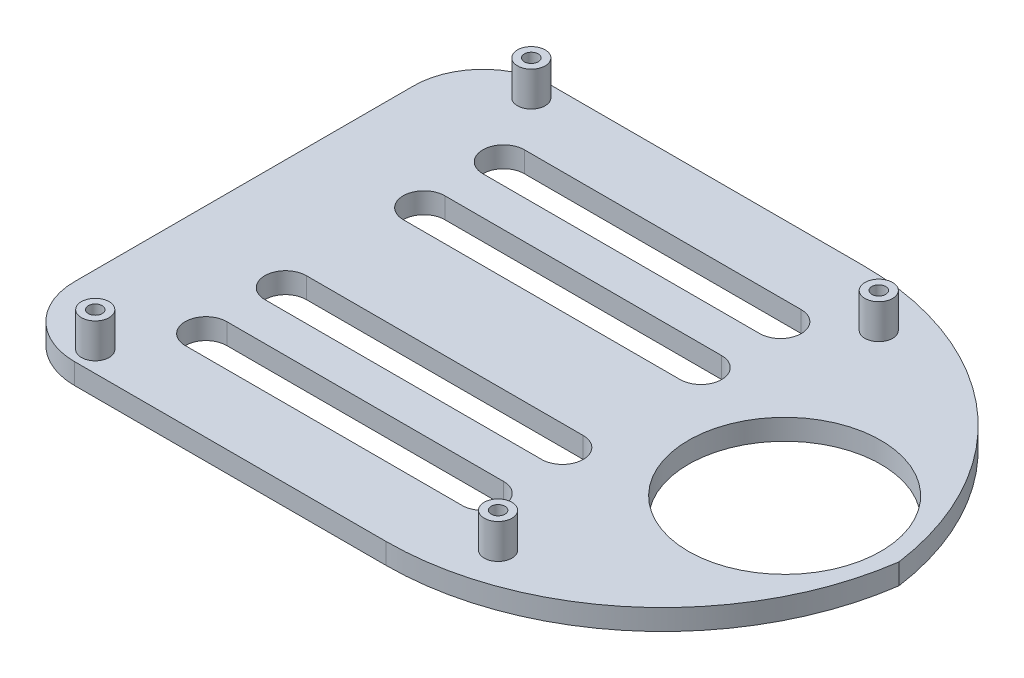
SolidWorks part; units mm, degrees
ref_plane "Plano frontal" through (0, 0, 0) normal (0, 0, 1) x (1, 0, 0)
ref_plane "Plano superior" through (0, 0, 0) normal (0, 1, 0) x (1, 0, 0)
ref_plane "Plano direito" through (0, 0, 0) normal (1, 0, 0) x (0, 0, -1)
sketch "Esboço1" plane through (0, 0, 0) normal (0, 1, 0) x (1, 0, 0)
  line L1 (-47.5, -34.5) -> (47.5, -34.5)
  line L2 (-47.5, -34.5) -> (-47.5, 34.5)
  line L3 (-47.5, 34.5) -> (47.5, 34.5)
  line L4 (47.5, -34.5) -> (47.5, 34.5)
  line L5 (-47.5, -34.5) -> (47.5, 34.5) construction
  line L6 (-47.5, 34.5) -> (47.5, -34.5) construction
  point P0 (0, 0)
  dimension "D1" = 95
  dimension "D2" = 69
extrude "Ressalto-extrusão1" add sketch "Esboço1" along normal blind 3
sketch "Esboço2" plane through (0, 3, 0) normal (0, 1, 0) x (1, 0, 0)
  line L0 (0, 0) -> (47.5, 0) construction
  line L1 (47.5, -34.5) -> (47.5, 34.5) construction
  circle A0 centre (30.6, 0) radius 13.9
  dimension "D1" = 27.8
  dimension "D2" = 16.9
extrude "Corte-extrusão1" cut sketch "Esboço2" against normal through all
sketch "Esboço4" plane through (0, 3, 0) normal (0, 1, 0) x (1, 0, 0)
  line L0 (16.7, 0) -> (16.7, 28.5) construction
  line L2 (47.5, 0) -> (-47.5, 0) construction
  line L3 (47.5, -34.5) -> (47.5, 34.5) construction
  line L4 (-47.5, 34.5) -> (-47.5, -34.5) construction
  line L7 (47.5, 34.5) -> (-47.5, 34.5) construction
  circle A2 centre (30.6, 0) radius 13.9 construction
  circle A3 centre (16.7, 27.5) radius 1
  circle A4 centre (16.7, -27.5) radius 1
  circle A5 centre (-37.5, 31.5) radius 1
  circle A6 centre (-37.5, -31.5) radius 1
  point P20 (0, 0)
  point P22 (0, 0)
  dimension "D1" = 28.5
  dimension "D2" = 2
  dimension "D3" = 2
  dimension "D4" = 3
  dimension "D5" = 10
extrude "Corte-extrusão2" cut sketch "Esboço4" against normal through all
sketch "Esboço5" plane through (0, 3, 0) normal (0, 1, 0) x (1, 0, 0)
  line L0 (47.5, 0) -> (-47.5, 0) construction
  line L1 (47.5, -34.5) -> (47.5, 34.5) construction
  line L2 (-47.5, 34.5) -> (-47.5, -34.5) construction
  circle A0 centre (-37.5, 31.5) radius 2
  circle A1 centre (-37.5, 31.5) radius 1
  circle A2 centre (16.7, 27.5) radius 1
  circle A3 centre (16.7, 27.5) radius 2
  circle A4 centre (16.7, -27.5) radius 2
  circle A5 centre (16.7, -27.5) radius 1
  circle A6 centre (-37.5, -31.5) radius 2
  circle A7 centre (-37.5, -31.5) radius 1
  dimension "D1" = 4
  dimension "D2" = 2
  dimension "D3" = 2
  dimension "D4" = 4
extrude "Ressalto-extrusão2" add sketch "Esboço5" along normal blind 5
fillet "Filete1" radius 40 2 edges at (47.5, 1.5, -34.5) (47.5, 1.5, 34.5)
fillet "Filete2" radius 10 2 edges at (-47.5, 1.5, 34.5) (-47.5, 1.5, -34.5)
sketch "Esboço7" plane through (0, 3, 0) normal (0, 1, 0) x (1, 0, 0)
  line L0 (16.7, 0) -> (-47.5, 0) construction
  line L1 (-47.5, 24.5) -> (-47.5, -24.5) construction
  line L2 (-31.5, 21.5) -> (8.5, 21.5) construction
  line L5 (-31.5, 10) -> (8.5, 10) construction
  line L6 (-31.5, 13) -> (8.5, 13)
  line L7 (-31.5, 7) -> (8.5, 7)
  line L8 (-31.5, 24.5) -> (8.5, 24.5)
  line L9 (-31.5, 18.5) -> (8.5, 18.5)
  line L10 (7.5, 34.5) -> (-37.5, 34.5) construction
  line L11 (-31.5, -21.5) -> (8.5, -21.5) construction
  line L12 (-31.5, -24.5) -> (8.5, -24.5)
  line L13 (-31.5, -18.5) -> (8.5, -18.5)
  line L14 (-31.5, -10) -> (8.5, -10) construction
  line L15 (-31.5, -13) -> (8.5, -13)
  line L16 (-31.5, -7) -> (8.5, -7)
  circle A0 centre (30.6, 0) radius 13.9 construction
  arc A3 (-31.5, 13) -> (-31.5, 7) centre (-31.5, 10) ccw
  arc A4 (8.5, 7) -> (8.5, 13) centre (8.5, 10) ccw
  arc A5 (-31.5, 24.5) -> (-31.5, 18.5) centre (-31.5, 21.5) ccw
  arc A6 (8.5, 18.5) -> (8.5, 24.5) centre (8.5, 21.5) ccw
  arc A7 (-31.5, -24.5) -> (-31.5, -18.5) centre (-31.5, -21.5) cw
  arc A8 (8.5, -18.5) -> (8.5, -24.5) centre (8.5, -21.5) cw
  arc A9 (-31.5, -13) -> (-31.5, -7) centre (-31.5, -10) cw
  arc A10 (8.5, -7) -> (8.5, -13) centre (8.5, -10) cw
  point P8 (-11.5, 21.5)
  point P15 (-11.5, 10)
  point P24 (-11.5, -21.5)
  point P31 (-11.5, -10)
  dimension "D5" = 16
  dimension "D1" = 10
  dimension "D2" = 3
  dimension "D3" = 40
  dimension "D4" = 7
  dimension "D6" = 16
extrude "Corte-extrusão3" cut sketch "Esboço7" against normal through all
